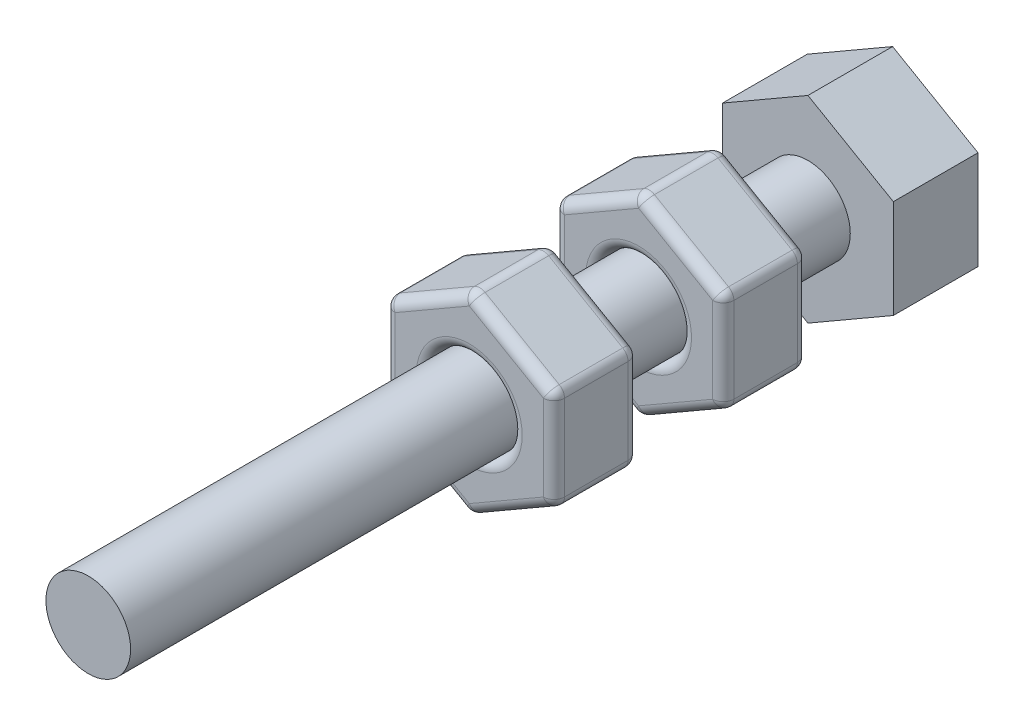
SolidWorks part; units mm, degrees
ref_plane "Front Plane" through (0, 0, 0) normal (0, 0, 1) x (1, 0, 0)
ref_plane "Top Plane" through (0, 0, 0) normal (0, 1, 0) x (1, 0, 0)
ref_plane "Right Plane" through (0, 0, 0) normal (1, 0, 0) x (0, 0, -1)
sketch "Sketch1" plane through (0, 0, 0) normal (0, 0, 1) x (1, 0, 0)
  line L1 (0, 4.6188) -> (-4, 2.3094)
  line L2 (-4, 2.3094) -> (-4, -2.3094)
  line L3 (-4, -2.3094) -> (0, -4.6188)
  line L4 (0, -4.6188) -> (4, -2.3094)
  line L5 (4, -2.3094) -> (4, 2.3094)
  line L6 (4, 2.3094) -> (0, 4.6188)
  circle A0 centre (0, 0) radius 4 construction
  circle A1 centre (0, 0) radius 2
  dimension "D1" = 8
  dimension "D2" = 4
extrude "Boss-Extrude1" add sketch "Sketch1" along normal mid plane 12
extrude "Cut-Extrude1" cut sketch "Sketch1<2>" against normal mid plane 4
sketch "Sketch1<2>" plane through (0, 0, 0) normal (0, 0, 1) x (1, 0, 0) same geometry as "Sketch1"
fillet "Fillet1" radius 0.5 20 edges at (0, -4.6188, 4) (-4, -2.3094, 4) (2, -3.4641, 6) (-2, -3.4641, 6) (-4, 0, 6) (2, 3.4641, 6) (-2, 3.4641, 6) (-4, 2.3094, 4) (0, 4.6188, 4) (4, 0, 6) (4, 2.3094, 4) (4, -2.3094, 4) (-2, 3.4641, 2) (-4, 0, 2) (-2, -3.4641, 2) (2, -3.4641, 2) (4, 0, 2) (2, 3.4641, 2) (2, 0, 2) (2, 0, 6)
fillet "Fillet2" radius 0.5 20 edges at (4, 2.3094, -4) (4, -2.3094, -4) (0, -4.6188, -4) (-4, -2.3094, -4) (-4, 2.3094, -4) (0, 4.6188, -4) (4, 0, -2) (2, -3.4641, -2) (-2, -3.4641, -2) (-4, 0, -2) (-2, 3.4641, -2) (2, 3.4641, -2) (2, 0, -2) (2, 0, -6) (-2, 3.4641, -6) (-4, 0, -6) (-2, -3.4641, -6) (2, -3.4641, -6) (4, 0, -6) (2, 3.4641, -6)
sketch "Sketch2" plane through (0, 0, 0) normal (0, 0, 1) x (1, 0, 0)
  circle A0 centre (0, 0) radius 2
extrude "Boss-Extrude2" add sketch "Sketch2" along normal blind 24 and the other way blind 14
sketch "Sketch3" plane through (0, 0, -14) normal (0, 0, -1) x (-1, 0, 0)
  line L1 (0, 4.6581) -> (-4.034, 2.329)
  line L2 (-4.034, 2.329) -> (-4.034, -2.329)
  line L3 (-4.034, -2.329) -> (0, -4.6581)
  line L4 (0, -4.6581) -> (4.034, -2.329)
  line L5 (4.034, -2.329) -> (4.034, 2.329)
  line L6 (4.034, 2.329) -> (0, 4.6581)
  circle A0 centre (0, 0) radius 4.034 construction
extrude "Boss-Extrude3" add sketch "Sketch3" against normal blind 4
